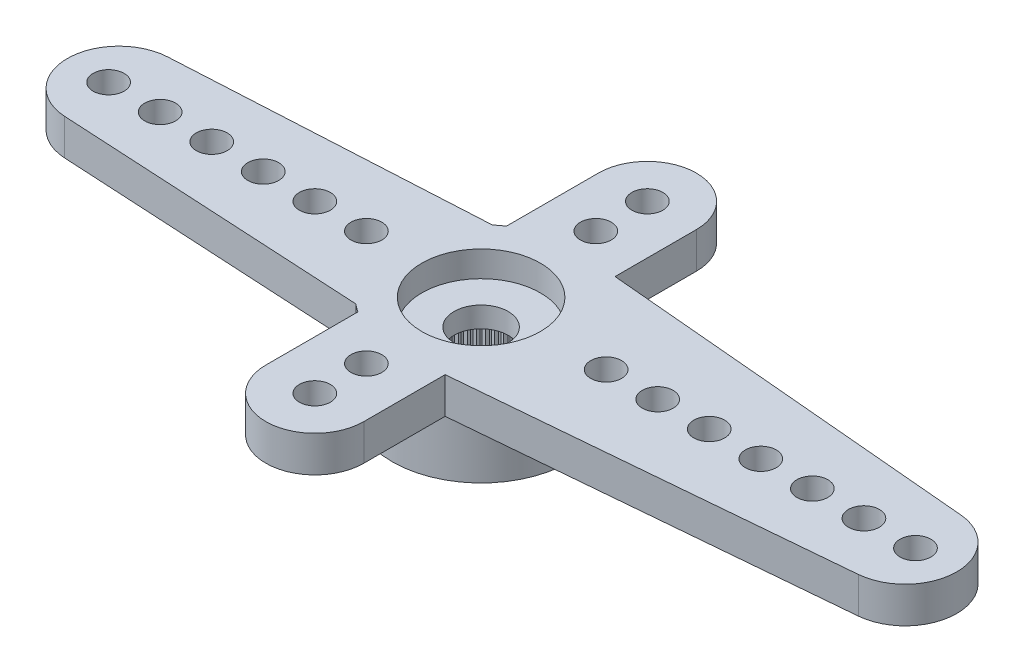
SolidWorks part; units mm, degrees
material "PVC Rígido"
ref_plane "Plano frontal" through (0, 0, 0) normal (0, 0, 1) x (1, 0, 0)
ref_plane "Plano superior" through (0, 0, 0) normal (0, 1, 0) x (1, 0, 0)
ref_plane "Plano direito" through (0, 0, 0) normal (1, 0, 0) x (0, 0, -1)
sketch "Esboço1" plane through (0, 0, 0) normal (0, 1, 0) x (1, 0, 0)
  line L0 (0, 0) -> (-14.05, 0) construction
  line L1 (-14.1591, 1.997) -> (-2.2091, 2.65)
  line L2 (-2.2091, -2.65) -> (-14.1591, -1.997)
  arc A0 (-2.2091, -2.65) -> (-2.2091, 2.65) centre (0, 0) ccw
  arc A1 (-14.1591, 1.997) -> (-14.1591, -1.997) centre (-14.05, 0) ccw
  dimension "D1" = 6.9
  dimension "D2" = 4
  dimension "D3" = 19.5
  dimension "D4" = 5.3
extrude "Ressalto-extrusão1" add sketch "Esboço1" against normal blind 1.4
sketch "Esboço2" plane through (0, -1.4, 0) normal (0, -1, 0) x (1, 0, 0)
  arc A0 (-2.2091, -2.65) -> (-2.2091, 2.65) centre (0, 0) ccw construction
  circle A1 centre (0, 0) radius 3.45
extrude "Ressalto-extrusão2" add sketch "Esboço2" along normal offset from surface (2.4 mm away) 3.8 up to face at (-7.242, 0, 0)
hole_wizard "Furo1" positions "Esboço9" profile "Esboço10" legacy end condition through all
sketch "Esboço9" plane through (0, 0, 0) normal (0, 1, 0) x (1, 0, 0)
  line L1 (-14.45, 0) -> (0, 0) construction
  arc A2 (-14.1591, 1.997) -> (-14.1591, -1.997) centre (-14.05, 0) ccw construction
  point P0 (-14.45, 0)
  point P19 (-16.05, 0)
  dimension "D1" = 1.6
sketch "Esboço10" plane through (-14.45, 0, 0) normal (1, 0, 0) x (0, 0, 1)
  line L0 (0, 0) -> (0, 3.8)
  line L1 (0, 3.8) -> (0.6, 3.8)
  line L2 (0.6, 3.8) -> (0.6, 0)
  line L3 (0.6, 0) -> (0, 0)
  line L4 (0, 110) -> (0, -10) construction
  dimension "Diameter" = 1.2
  dimension "Depth" = 3.8
pattern_linear "Padrão linear1" count 6 spacing 2 along (1, 0, 0) of "Furo1"
sketch "Esboço12" plane through (0, 0, 0) normal (0, 1, 0) x (1, 0, 0)
  line L0 (0.3041, 3.4366) -> (16.6263, 1.9922)
  line L1 (16.6263, -1.9922) -> (0.3041, -3.4366)
  arc A0 (-2.2091, -2.65) -> (-2.2091, 2.65) centre (0, 0) ccw construction
  arc A1 (0.3041, -3.4366) -> (0.3041, 3.4366) centre (0, 0) ccw
  arc A2 (16.6263, 1.9922) -> (16.6263, -1.9922) centre (16.45, 0) cw
  arc A3 (-14.1591, 1.997) -> (-14.1591, -1.997) centre (-14.05, 0) ccw construction
  dimension "D1" = 2
  dimension "D2" = 34.5
extrude "Ressalto-extrusão3" add sketch "Esboço12" against normal up to surface (1.4 mm away) up to face at (-12.45, -1.4, 0.6)
hole_wizard "Furo2" positions "Esboço13" profile "Esboço14" legacy end condition through all
sketch "Esboço13" plane through (0, 0, 0) normal (0, 1, 0) x (1, 0, 0)
  line L0 (0, 0) -> (16.85, 0) construction
  arc A0 (16.6263, -1.9922) -> (16.6263, 1.9922) centre (16.45, 0) ccw construction
  point P0 (16.85, 0)
  point P6 (18.45, 0)
  dimension "D1" = 1.6
sketch "Esboço14" plane through (16.85, 0, 0) normal (1, 0, 0) x (0, 0, 1)
  line L0 (0, 0) -> (0, 3.8)
  line L1 (0, 3.8) -> (0.6, 3.8)
  line L2 (0.6, 3.8) -> (0.6, 0)
  line L3 (0.6, 0) -> (0, 0)
  line L4 (0, 110) -> (0, -10) construction
  dimension "Diameter" = 1.2
  dimension "Depth" = 3.8
pattern_linear "Padrão linear2" count 7 spacing 2 along (-1, 0, 0) of "Furo2"
sketch "Esboço16" plane through (0, 0, 0) normal (0, 1, 0) x (1, 0, 0)
  line L0 (0, -6.45) -> (0, 6.45) construction
  line L1 (-1.9, -6.45) -> (-1.9, 6.45)
  line L2 (1.9, -6.45) -> (1.9, 6.45)
  arc A0 (-1.9, -6.45) -> (1.9, -6.45) centre (0, -6.45) ccw
  arc A1 (1.9, 6.45) -> (-1.9, 6.45) centre (0, 6.45) ccw
  point P2 (0, 0)
  dimension "D2" = 16.7
  dimension "D1" = 3.8
extrude "Ressalto-extrusão4" add sketch "Esboço16" against normal up to surface (1.4 mm away) up to face at (14.85, -1.4, 0.6)
hole_wizard "Furo3" positions "Esboço17" profile "Esboço18" legacy end condition through all
sketch "Esboço17" plane through (0, 0, 0) normal (0, 1, 0) x (1, 0, 0)
  point P0 (0, -6.45)
sketch "Esboço18" plane through (0, 0, 6.45) normal (1, 0, 0) x (0, 0, 1)
  line L0 (0, 0) -> (0, 3.8)
  line L1 (0, 3.8) -> (0.6, 3.8)
  line L2 (0.6, 3.8) -> (0.6, 0)
  line L3 (0.6, 0) -> (0, 0)
  line L4 (0, 110) -> (0, -10) construction
  dimension "Diameter" = 1.2
  dimension "Depth" = 3.8
pattern_linear "Padrão linear3" count 2 spacing 2 along (0, 0, -1) of "Furo3"
pattern_circular "PadrãoCircular1" count 2 over 360 about axis through (0, -1.4, 0) along (0, 1, 0) of "Padrão linear3"
hole_wizard "Furo4" positions "Esboço3" profile "Esboço4" legacy
sketch "Esboço3" plane through (0, -3.8, 0) normal (0, -1, 0) x (-1, 0, 0)
  point P0 (0, 0)
sketch "Esboço4" plane through (0, -3.8, 0) normal (1, 0, 0) x (0, 0, -1)
  line L0 (0, 0) -> (0, 2)
  line L1 (0, 2) -> (2.475, 2)
  line L2 (2.475, 2) -> (2.475, 0)
  line L3 (2.475, 0) -> (0, 0)
  line L4 (0, 110) -> (0, -10) construction
  dimension "Diameter" = 4.95
  dimension "Depth" = 2
hole_wizard "Furo5" positions "Esboço5" profile "Esboço6" legacy
sketch "Esboço5" plane through (0, 0, 0) normal (0, 1, 0) x (1, 0, 0)
  point P0 (0, 0)
sketch "Esboço6" plane through (0, 0, 0) normal (1, 0, 0) x (0, 0, 1)
  line L0 (0, 0) -> (0, 1)
  line L1 (0, 1) -> (2.3, 1)
  line L2 (2.3, 1) -> (2.3, 0)
  line L3 (2.3, 0) -> (0, 0)
  line L4 (0, 110) -> (0, -10) construction
  dimension "Diameter" = 4.6
  dimension "Depth" = 1
hole_wizard "Furo6" positions "Esboço7" profile "Esboço8" legacy end condition through all
sketch "Esboço7" plane through (0, 0, 0) normal (0, 1, 0) x (1, 0, 0)
  point P0 (0, 0)
sketch "Esboço8" plane through (0, 0, 0) normal (1, 0, 0) x (0, 0, 1)
  line L0 (0, 0) -> (0, 3.8)
  line L1 (0, 3.8) -> (1.05, 3.8)
  line L2 (1.05, 3.8) -> (1.05, 0)
  line L3 (1.05, 0) -> (0, 0)
  line L4 (0, 110) -> (0, -10) construction
  dimension "Diameter" = 2.1
  dimension "Depth" = 3.8
sketch "Esboço11" plane through (0, -3.8, 0) normal (0, -1, 0) x (1, 0, 0)
  line L0 (-0.0981, 2.4731) -> (0, 2.375)
  line L1 (0, 2.375) -> (0.0981, 2.4731)
  line L2 (0, 0) -> (0, 2.475) construction
  circle A0 centre (0, 0) radius 2.375 construction
  circle A1 centre (0, 0) radius 2.475
  arc A2 (0.0981, 2.4731) -> (-0.0981, 2.4731) centre (0, 0) ccw
  dimension "D3" = 4.75
  dimension "D2" = 0.1
  dimension "D1" = 0
extrude "Ressalto-extrusão5" add sketch "Esboço11" against normal up to surface (2 mm away) up to face at (0, -1.8, 1.05)
pattern_circular "PadrãoCircular2" count 60 over 360 about axis through (0, -1.4, 0) along (0, 1, 0) of "Ressalto-extrusão5"
